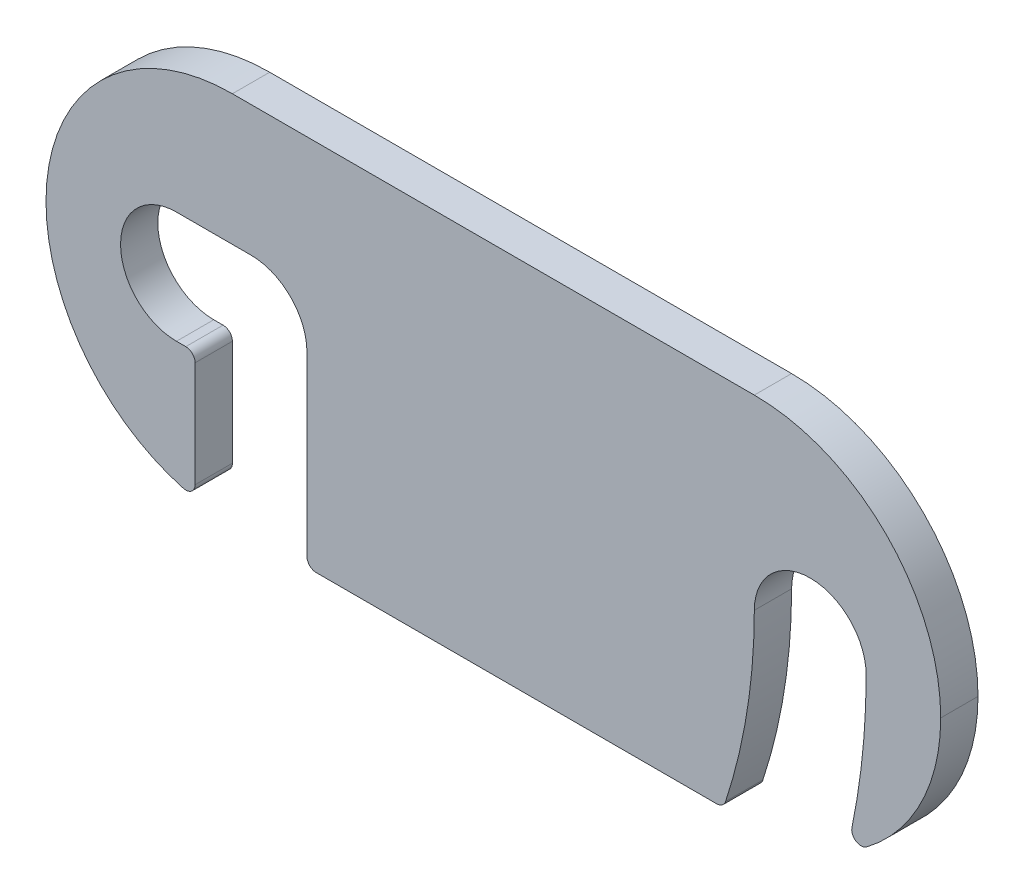
SolidWorks part; units mm, degrees
ref_plane "Płaszczyzna przednia" through (0, 0, 0) normal (0, 0, 1) x (1, 0, 0)
ref_plane "Płaszczyzna górna" through (0, 0, 0) normal (0, 1, 0) x (1, 0, 0)
ref_plane "Płaszczyzna prawa" through (0, 0, 0) normal (1, 0, 0) x (0, 0, -1)
sketch "Szkic1" plane through (0, 0, 0) normal (0, 0, 1) x (1, 0, 0)
  line L0 (0, 0) -> (0, -10)
  line L1 (0, 0) -> (-48, 0)
  line L2 (0, 0) -> (0, -20)
  line L3 (0, -20) -> (-48, -20)
  line L4 (-48, 0) -> (-48, -20)
  line L5 (0, -10) -> (-7, -10)
  line L6 (-48, 0) -> (-48, -10)
  line L7 (-48, -10) -> (-41, -10)
  circle A2 centre (-7, -10) radius 3
  circle A3 centre (-41, -10) radius 3
  dimension "D1" = 48
  dimension "D2" = 20
  dimension "D5" = 6
  dimension "D6" = 6
  dimension "D3" = 7
  dimension "D4" = 7
extrude "Dodanie-wyciągnięcie2" add sketch "Szkic1" along normal blind 2 contours A3 L4 L3 L2 A2 L0 L1 region at (-24, -10, 0)
fillet "Zaokrąglenie3" radius 10 4 edges at (0, 0, 1) (0, -20, 1) (-48, -20, 1) (-48, 0, 1)
sketch "Szkic2" plane through (0, 0, 2) normal (0, 0, 1) x (1, 0, 0)
  line L9 (-10, -10) -> (-4, -10)
  line L10 (-11.6572, -20) -> (-5.377, -20)
  line L11 (-10, -20) -> (-38, -20) construction
  line L12 (-41, -10) -> (-41, -13)
  line L13 (-41, -13) -> (-40, -13)
  line L14 (-34, -17.5) -> (-34, -7)
  line L15 (-34, -7) -> (-41, -7)
  line L16 (-41, -7) -> (-41, -10)
  line L19 (-34, -17.5) -> (-34, -20)
  line L20 (-34, -20) -> (-40, -20)
  line L21 (-40, -13) -> (-40, -20)
  arc A2 (-11.6572, -20) -> (-10, -10) centre (-41, -10) ccw
  arc A3 (-5.377, -20) -> (-4, -10) centre (-41, -10) ccw
  circle A4 centre (-41, -10) radius 3 construction
  dimension "D3" = 62
  dimension "D4" = 74
  dimension "D1" = 6
  dimension "D2" = 7
extrude "Wytnij-wyciągnięcie1" cut sketch "Szkic2" against normal through all
fillet "Zaokrąglenie1" radius 3 1 edges at (-34, -7, 1)
fillet "Zaokrąglenie2" radius 0.5 5 edges at (-11.6572, -20, 1) (-34, -20, 1) (-5.0323, -18.6788, 1) (-40, -13, 1) (-40, -19.798, 1)
